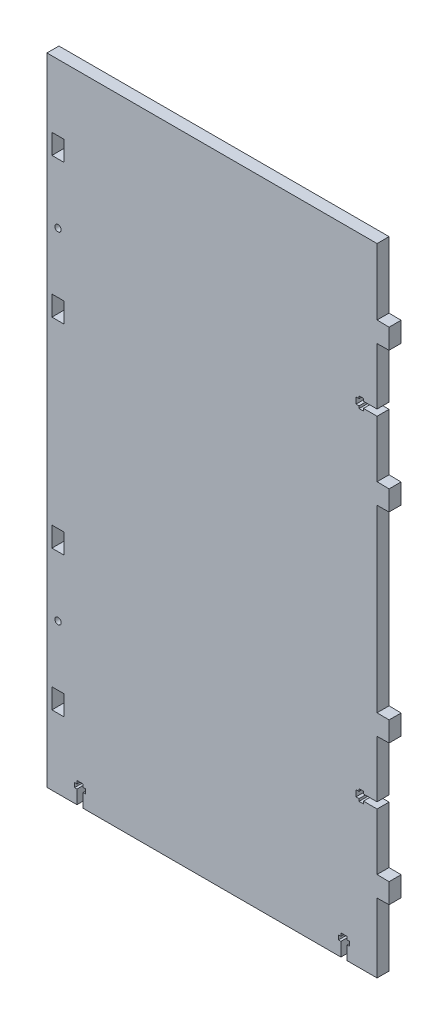
SolidWorks part; units mm, degrees
material "Клен"
ref_plane "Front" through (0, 0, 0) normal (0, 0, 1) x (1, 0, 0)
ref_plane "Top" through (0, 0, 0) normal (0, 1, 0) x (1, 0, 0)
ref_plane "Right" through (0, 0, 0) normal (1, 0, 0) x (0, 0, -1)
sketch "Эскиз1" plane through (0, 0, 0) normal (0, 0, 1) x (1, 0, 0)
  line L16 (922.3199, 553.2385) -> (922.3199, 563.2385)
  line L17 (916.2199, 553.2385) -> (922.3199, 553.2385)
  line L18 (916.2199, 563.2385) -> (916.2199, 553.2385)
  line L19 (922.3199, 563.2385) -> (916.2199, 563.2385)
  line L20 (916.2199, 623.2385) -> (922.3199, 623.2385)
  line L21 (922.3199, 623.2385) -> (922.3199, 633.2385)
  line L22 (922.3199, 633.2385) -> (916.2199, 633.2385)
  line L23 (916.2199, 633.2385) -> (916.2199, 623.2385)
  line L24 (916.2199, 723.2385) -> (922.3199, 723.2385)
  line L25 (922.3199, 723.2385) -> (922.3199, 733.2385)
  line L26 (916.2199, 733.2385) -> (916.2199, 723.2385)
  line L27 (922.3199, 733.2385) -> (916.2199, 733.2385)
  line L28 (922.3199, 793.2385) -> (922.3199, 803.2385)
  line L29 (922.3199, 803.2385) -> (916.2199, 803.2385)
  line L30 (916.2199, 803.2385) -> (916.2199, 793.2385)
  line L31 (916.2199, 793.2385) -> (922.3199, 793.2385)
  line L32 (978.7199, 858.5777) -> (978.7199, 499.7864) construction
  line L33 (1078.7199, 858.5777) -> (1078.7199, 499.7864) construction
  line L34 (1078.7199, 623.0385) -> (1084.7199, 623.1385)
  line L35 (1068.2199, 764.6885) -> (1069.7199, 764.6885)
  line L36 (1084.7199, 553.1385) -> (1084.7199, 563.1385)
  line L37 (1071.9199, 591.5885) -> (1071.9199, 590.3885)
  line L38 (1071.9199, 761.5885) -> (1071.9199, 760.3885)
  line L39 (1071.9199, 765.8885) -> (1071.9199, 764.6885)
  line L40 (1084.7199, 793.1385) -> (1084.7199, 803.1385)
  line L41 (1084.7199, 723.1385) -> (1084.7199, 733.1385)
  line L42 (1068.2199, 761.5885) -> (1068.2199, 764.6885)
  line L43 (1069.7199, 590.3885) -> (1069.7199, 591.5885)
  line L44 (1068.2199, 591.5885) -> (1068.2199, 594.6885)
  line L45 (1084.7199, 733.1385) -> (1078.7199, 733.2385)
  line L46 (1084.7199, 633.1385) -> (1078.7199, 633.2385)
  line L47 (1078.7199, 633.2385) -> (1078.7199, 723.0385)
  line L48 (1084.7199, 803.1385) -> (1078.7199, 803.2385)
  line L49 (1071.9199, 595.8885) -> (1071.9199, 594.6885)
  line L50 (1078.7199, 793.0385) -> (1084.7199, 793.1385)
  line L51 (1078.7199, 733.2385) -> (1078.7199, 761.5885)
  line L52 (1068.2199, 594.6885) -> (1069.7199, 594.6885)
  line L53 (1071.9199, 760.3885) -> (1069.7199, 760.3885)
  line L54 (1069.7199, 761.5885) -> (1068.2199, 761.5885)
  line L55 (1069.7199, 765.8885) -> (1071.9199, 765.8885)
  line L112 (931.8199, 525.2362) -> (931.8199, 518.4362)
  line L113 (931.8199, 518.4362) -> (978.7199, 518.4362)
  line L155 (978.7199, 836.3385) -> (913.7199, 836.3385)
  line L156 (913.7199, 836.3385) -> (913.7199, 518.4362)
  line L157 (913.7199, 518.4362) -> (928.7199, 518.4362)
  line L158 (928.7199, 518.4362) -> (928.7199, 525.2362)
  line L159 (928.7199, 525.2362) -> (927.5199, 525.2362)
  line L160 (927.5199, 525.2362) -> (927.5199, 527.4362)
  line L161 (927.5199, 527.4362) -> (928.7199, 527.4362)
  line L162 (928.7199, 527.4362) -> (928.7199, 528.9362)
  line L163 (928.7199, 528.9362) -> (931.8199, 528.9362)
  line L164 (931.8199, 528.9362) -> (931.8199, 527.4362)
  line L165 (931.8199, 527.4362) -> (933.0199, 527.4362)
  line L166 (933.0199, 527.4362) -> (933.0199, 525.2362)
  line L167 (933.0199, 525.2362) -> (931.8199, 525.2362)
  line L168 (1069.7199, 594.6885) -> (1069.7199, 595.8885)
  line L169 (1078.7199, 594.6885) -> (1078.7199, 623.0385)
  line L170 (1071.9199, 764.6885) -> (1078.7199, 764.6885)
  line L171 (1084.7199, 563.1385) -> (1078.7199, 563.2385)
  line L172 (1084.7199, 623.1385) -> (1084.7199, 633.1385)
  line L173 (1069.7199, 764.6885) -> (1069.7199, 765.8885)
  line L174 (1078.7199, 553.0385) -> (1084.7199, 553.1385)
  line L175 (1078.7199, 563.2385) -> (1078.7199, 591.5885)
  line L176 (1078.7199, 761.5885) -> (1071.9199, 761.5885)
  line L177 (1078.7199, 518.4362) -> (1078.7199, 553.0385)
  line L178 (1069.7199, 591.5885) -> (1068.2199, 591.5885)
  line L179 (1069.7199, 595.8885) -> (1071.9199, 595.8885)
  line L180 (1069.7199, 760.3885) -> (1069.7199, 761.5885)
  line L181 (1078.7199, 591.5885) -> (1071.9199, 591.5885)
  line L182 (1071.9199, 594.6885) -> (1078.7199, 594.6885)
  line L183 (1078.7199, 803.2385) -> (1078.7199, 836.3385)
  line L184 (1071.9199, 590.3885) -> (1069.7199, 590.3885)
  line L185 (1078.7199, 723.0385) -> (1084.7199, 723.1385)
  line L186 (1078.7199, 764.6885) -> (1078.7199, 793.0385)
  line L187 (978.7199, 836.3385) -> (1078.7199, 836.3385)
  line L188 (978.7199, 518.4362) -> (1060.6199, 518.4362)
  line L189 (1059.4199, 527.4362) -> (1060.6199, 527.4362)
  line L190 (1060.6199, 518.4362) -> (1060.6199, 525.2362)
  line L191 (1064.9199, 525.2362) -> (1063.7199, 525.2362)
  line L192 (1060.6199, 527.4362) -> (1060.6199, 528.9362)
  line L193 (1060.6199, 528.9362) -> (1063.7199, 528.9362)
  line L194 (1060.6199, 525.2362) -> (1059.4199, 525.2362)
  line L195 (1063.7199, 525.2362) -> (1063.7199, 518.4362)
  line L196 (1063.7199, 528.9362) -> (1063.7199, 527.4362)
  line L197 (1063.7199, 527.4362) -> (1064.9199, 527.4362)
  line L198 (1059.4199, 525.2362) -> (1059.4199, 527.4362)
  line L199 (1064.9199, 527.4362) -> (1064.9199, 525.2362)
  line L200 (1063.7199, 518.4362) -> (1078.7199, 518.4362)
  circle A2 centre (919.2699, 593.2385) radius 1.6
  circle A3 centre (919.2699, 763.2385) radius 1.6
  dimension "D2" = 100
  dimension "D3" = 65
  dimension "D4" = 15
extrude "Бобышка-Вытянуть1" add sketch "Эскиз1" along normal blind 6
